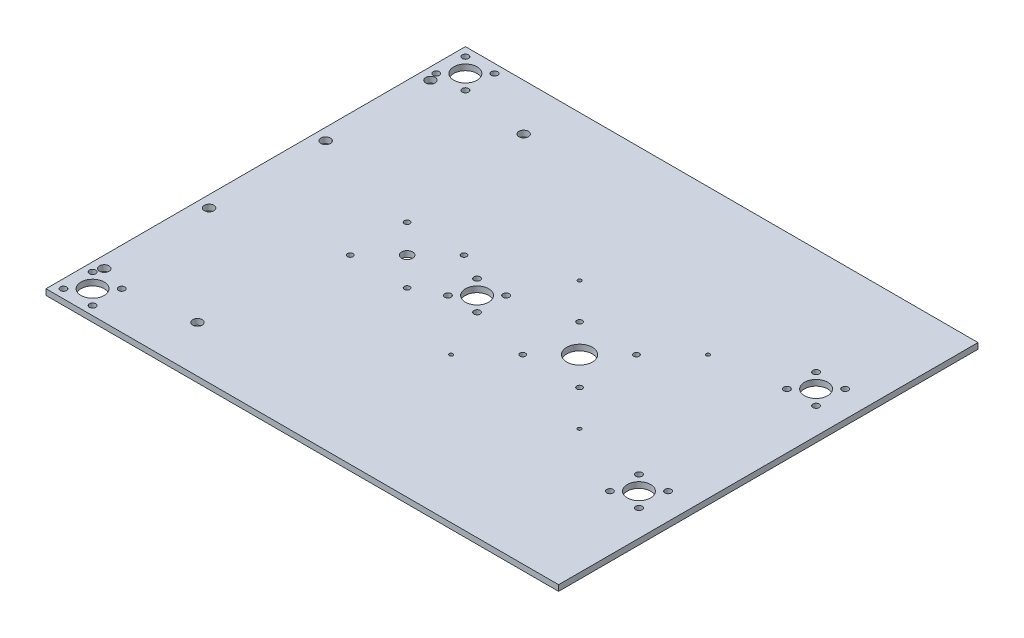
SolidWorks part; units mm, degrees
ref_plane "Front Plane" through (0, 0, 0) normal (0, 0, 1) x (1, 0, 0)
ref_plane "Top Plane" through (0, 0, 0) normal (0, 1, 0) x (1, 0, 0)
ref_plane "Right Plane" through (0, 0, 0) normal (1, 0, 0) x (0, 0, -1)
sketch "Sketch1" plane through (0, 0, 0) normal (0, 1, 0) x (1, 0, 0)
  line L1 (-139.7, -114.3) -> (139.7, -114.3)
  line L2 (-139.7, -114.3) -> (-139.7, 114.3)
  line L3 (-139.7, 114.3) -> (139.7, 114.3)
  line L4 (139.7, -114.3) -> (139.7, 114.3)
  line L5 (-139.7, -114.3) -> (139.7, 114.3) construction
  line L6 (-139.7, 114.3) -> (139.7, -114.3) construction
  point P0 (0, 0)
  dimension "D1" = 228.6
  dimension "D2" = 279.4
extrude "Boss-Extrude1" add sketch "Sketch1" along normal blind 3.175
sketch "Sketch2" plane through (0, 0, 0) normal (0, 1, 0) x (1, 0, 0)
  line L0 (-193.2668, 0) -> (192.9727, 0) construction
sketch "Sketch3" plane through (0, 3.175, 0) normal (0, 1, 0) x (1, 0, 0)
  circle A1 centre (-133.35, -31.75) radius 2.6
  circle A2 centre (-133.35, -31.75) radius 2.6
  circle A3 centre (-82.55, -88.9) radius 2.6
  circle A4 centre (-82.55, -88.9) radius 2.6
  circle A5 centre (-133.35, -88.9) radius 2.6
  circle A6 centre (-133.35, -88.9) radius 2.6
  dimension "D1" = 0
  dimension "D2" = 0
  dimension "D3" = 0
sketch "Sketch5" plane through (0, 3.175, 0) normal (0, 1, 0) x (1, 0, 0)
  circle A0 centre (-41.674, 15.5) radius 1.5 construction
  circle A1 centre (-41.674, -15.5) radius 1.5 construction
  circle A2 centre (-72.674, 15.5) radius 1.5 construction
  circle A3 centre (-72.674, -15.5) radius 1.5 construction
  circle A4 centre (-57.174, 0) radius 2.5 construction
  circle A5 centre (-41.674, 15.5) radius 1.5
  circle A6 centre (-41.674, -15.5) radius 1.5
  circle A7 centre (-72.674, 15.5) radius 1.5
  circle A8 centre (-72.674, -15.5) radius 1.5
  circle A9 centre (-57.174, 0) radius 2.5 construction
  circle A10 centre (-57.174, 0) radius 3.008
  dimension "D1" = 6.016
sketch "Sketch7" plane through (0, 3.175, 0) normal (0, 1, 0) x (1, 0, 0)
  circle A0 centre (71.8318, -35.0018) radius 1 construction
  circle A1 centre (1.8282, -35.0018) radius 1 construction
  circle A2 centre (71.8318, -35.0018) radius 1
  circle A3 centre (1.8282, -35.0018) radius 1
  circle A4 centre (1.8282, 35.0018) radius 1 construction
  circle A5 centre (71.8318, 35.0018) radius 1 construction
  circle A6 centre (1.8282, 35.0018) radius 1
  circle A7 centre (71.8318, 35.0018) radius 1
extrude "Cut-Extrude1" cut sketch "Sketch3" against normal through all
mirror "Mirror1" about plane through (0, 0, 0) normal (0, 0, 1) of "Cut-Extrude1"
extrude "Cut-Extrude2" cut sketch "Sketch5" against normal through all
extrude "Cut-Extrude3" cut sketch "Sketch7" against normal through all
sketch "Sketch9" plane through (0, 3.175, 0) normal (0, 1, 0) x (1, 0, 0)
  circle A0 centre (-119.0625, -109.5375) radius 1.727 construction
  circle A1 centre (-119.0625, -93.6625) radius 1.727 construction
  circle A2 centre (-134.9375, -93.6625) radius 1.727 construction
  circle A3 centre (-134.9375, -109.5375) radius 1.727 construction
  circle A4 centre (-127, -101.6) radius 6.35 construction
  circle A5 centre (-119.0625, -109.5375) radius 1.727
  circle A6 centre (-119.0625, -93.6625) radius 1.727
  circle A7 centre (-134.9375, -93.6625) radius 1.727
  circle A8 centre (-134.9375, -109.5375) radius 1.727
  circle A9 centre (-127, -101.6) radius 6.35
  circle A10 centre (125.4125, -56.1975) radius 1.727 construction
  circle A11 centre (125.4125, -40.3225) radius 1.727 construction
  circle A12 centre (117.475, -48.26) radius 6.35 construction
  circle A13 centre (109.5375, -40.3225) radius 1.727 construction
  circle A14 centre (109.5375, -56.1975) radius 1.727 construction
  circle A15 centre (125.4125, -56.1975) radius 1.727
  circle A16 centre (125.4125, -40.3225) radius 1.727
  circle A17 centre (117.475, -48.26) radius 6.35
  circle A18 centre (109.5375, -40.3225) radius 1.727
  circle A19 centre (109.5375, -56.1975) radius 1.727
  circle A20 centre (-11.1125, 7.9375) radius 1.727 construction
  circle A21 centre (-11.1125, -7.9375) radius 1.727 construction
  circle A22 centre (-19.05, 0) radius 6.35 construction
  circle A23 centre (-26.9875, -7.9375) radius 1.727 construction
  circle A24 centre (-26.9875, 7.9375) radius 1.727 construction
  circle A25 centre (-11.1125, 7.9375) radius 1.727
  circle A26 centre (-11.1125, -7.9375) radius 1.727
  circle A27 centre (-19.05, 0) radius 6.35
  circle A28 centre (-26.9875, -7.9375) radius 1.727
  circle A29 centre (-26.9875, 7.9375) radius 1.727
  circle A30 centre (109.5375, 56.1975) radius 1.727 construction
  circle A31 centre (109.5375, 40.3225) radius 1.727 construction
  circle A32 centre (125.4125, 56.1975) radius 1.727 construction
  circle A33 centre (117.475, 48.26) radius 6.35 construction
  circle A34 centre (125.4125, 40.3225) radius 1.727 construction
  circle A35 centre (109.5375, 56.1975) radius 1.727
  circle A36 centre (109.5375, 40.3225) radius 1.727
  circle A37 centre (125.4125, 56.1975) radius 1.727
  circle A38 centre (117.475, 48.26) radius 6.35
  circle A39 centre (125.4125, 40.3225) radius 1.727
  circle A40 centre (-119.0625, 93.6625) radius 1.727 construction
  circle A41 centre (-119.0625, 109.5375) radius 1.727 construction
  circle A42 centre (-134.9375, 109.5375) radius 1.727 construction
  circle A43 centre (-134.9375, 93.6625) radius 1.727 construction
  circle A44 centre (-119.0625, 93.6625) radius 1.727
  circle A45 centre (-119.0625, 109.5375) radius 1.727
  circle A46 centre (-134.9375, 109.5375) radius 1.727
  circle A47 centre (-134.9375, 93.6625) radius 1.727
  circle A48 centre (-127, 101.6) radius 6.35 construction
  circle A49 centre (-127, 101.6) radius 6.35
extrude "Cut-Extrude5" cut sketch "Sketch9" against normal through all both and the other way through all
sketch "Sketch11" plane through (0, 3.175, 0) normal (0, 1, 0) x (1, 0, 0)
  circle A0 centre (52.33, 15.5) radius 1.5 construction
  circle A1 centre (52.33, -15.5) radius 1.5 construction
  circle A2 centre (21.33, -15.5) radius 1.5 construction
  circle A3 centre (21.33, 15.5) radius 1.5 construction
  circle A4 centre (36.83, 0) radius 5.25 construction
  circle A5 centre (52.33, 15.5) radius 1.5
  circle A6 centre (52.33, -15.5) radius 1.5
  circle A7 centre (21.33, -15.5) radius 1.5
  circle A8 centre (21.33, 15.5) radius 1.5
  circle A9 centre (36.83, 0) radius 5.25 construction
  circle A10 centre (36.83, 0) radius 6.985
  dimension "D1" = 13.97
extrude "Cut-Extrude6" cut sketch "Sketch11" against normal through all both and the other way through all
equation "\"tightTol\"= 0.005in"
equation "\"normTol\"= 0.01in"
equation "\"looseTol\"= 0.02in"
equation "\"D1@Sketch5\"=5mm+2*\"looseTol\""
